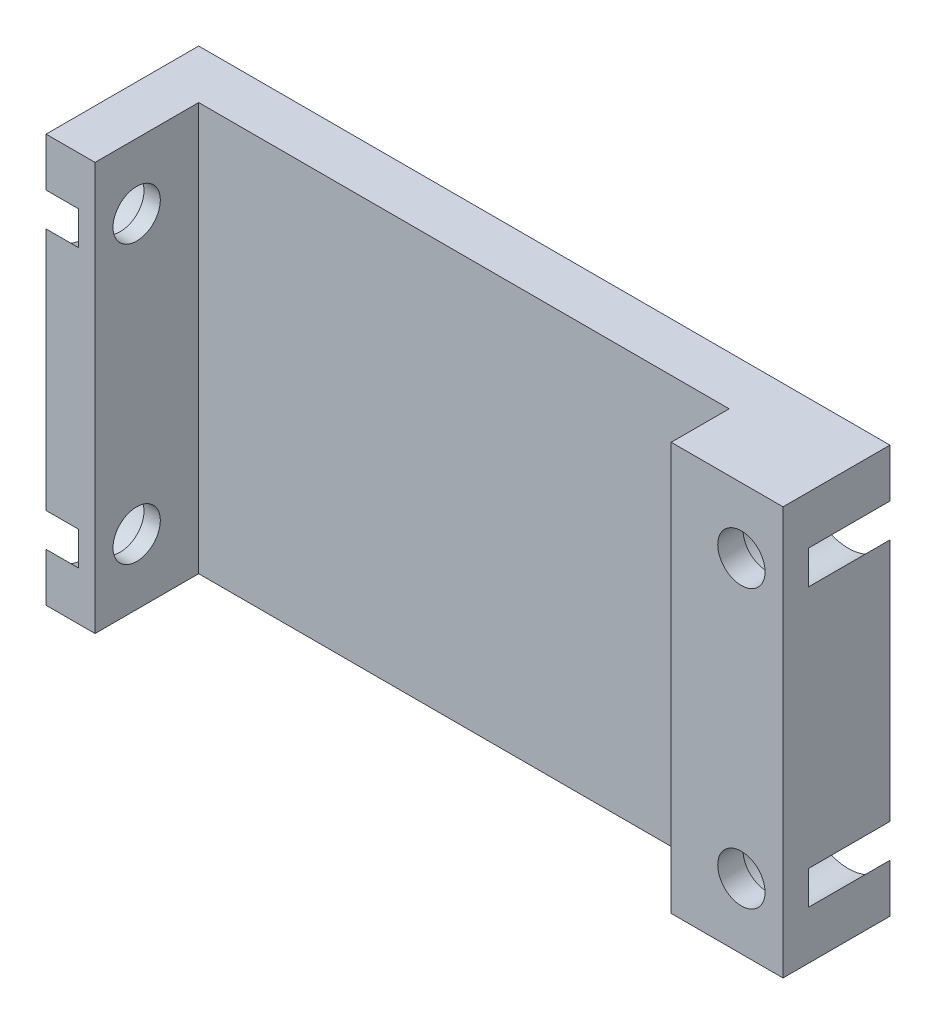
SolidWorks part; units mm, degrees
ref_plane "Plano frontal" through (0, 0, 0) normal (0, 0, 1) x (1, 0, 0)
ref_plane "Plano superior" through (0, 0, 0) normal (0, 1, 0) x (1, 0, 0)
ref_plane "Plano direito" through (0, 0, 0) normal (1, 0, 0) x (0, 0, -1)
sketch "Esboço2" plane through (0, 0, 0) normal (0, 0, 1) x (1, 0, 0)
  line L0 (0, 0) -> (0, -38.6) construction
  line L1 (-1.5, -22.5) -> (5.3501, -22.5)
  line L2 (-1.5, -22.5) -> (-1.5, 2.5)
  line L3 (-1.5, 2.5) -> (5.3501, 2.5)
  line L4 (5.3501, -22.5) -> (5.3501, 2.5)
  line L5 (2.8, -1.5) -> (2.8, 2.5) construction
  line L6 (2.8, -18.5) -> (2.8, -22.5) construction
  dimension "D1" = 0.25
  dimension "D2" = 4
  dimension "D3" = 1.5
extrude "Ressalto-extrusão2" add sketch "Esboço2" against normal offset from surface (3.55 mm away) 1 from offset 0.25 offset beyond the face yes offset against normal yes
sketch "Esboço3" plane through (0, 0, -3.8) normal (0, 0, -1) x (-1, 0, 0)
  line L0 (33.75, 0) -> (33.75, -38.6) construction
  line L1 (-5.3501, 2.5) -> (34, 2.5)
  line L2 (-5.3501, 2.5) -> (-5.3501, -22.5)
  line L3 (-5.3501, -22.5) -> (34, -22.5)
  line L4 (34, 2.5) -> (34, -22.5)
  line L5 (-5.3501, -22.5) -> (1.5, -22.5) construction
  dimension "D1" = 0.25
extrude "Ressalto-extrusão3" add sketch "Esboço3" along normal blind 3
sketch "Esboço4" plane through (-34, 0, 0) normal (-1, 0, 0) x (0, 0, 1)
  line L1 (-6.8, -22.5) -> (2.55, -22.5)
  line L2 (-6.8, -22.5) -> (-6.8, 2.5)
  line L3 (-6.8, 2.5) -> (2.55, 2.5)
  line L4 (2.55, -22.5) -> (2.55, 2.5)
  line L5 (-6.8, 2.5) -> (-3.8, 2.5) construction
  dimension "D1" = 0.25
extrude "Ressalto-extrusão4" add sketch "Esboço4" along normal blind 3
hole_wizard "CBORE for M2.5 SHCS2" positions "3DSketch1" profile "Sketch1" counterbore size "M2.5" standard "ANSI Metric"
sketch3d "3DSketch1"
  circle A0 centre (-33.75, -1.5, 0) radius 1.35 construction
  circle A1 centre (-33.75, -18.5, 0) radius 1.35 construction
  point P0 (-37, -1.5, 0)
  point P7 (-32.4, -1.5, 0)
  point P8 (-37, -18.5, 0)
  point P20 (-32.4, -18.5, 0)
sketch "Sketch1" plane through (-37, -1.5, 0) normal (0, 1, 0) x (0, 0, 1)
  line L0 (0, 0) -> (0, 3.8712)
  line L1 (0, 3.8712) -> (1.45, 3)
  line L2 (1.45, 3) -> (1.45, 2)
  line L3 (1.45, 2) -> (2.75, 2)
  line L4 (2.75, 2) -> (2.75, 0)
  line L5 (2.75, 0) -> (0, 0)
  line L10 (0, 3.8712) -> (-1.45, 3) construction
  line L11 (0, -6.35) -> (0, 107.95) construction
  dimension "Hole Dia." = 2.9
  dimension "Hole Depth" = 3
  dimension "C'Bore Dia." = 5.5
  dimension "C'Bore Depth" = 2
  dimension "Drill Angle" = 118
hole_wizard "CBORE for M2.5 SHCS3" positions "Sketch2" profile "Sketch4" counterbore size "M2.5" standard "ANSI Metric" end condition up to next
sketch "Sketch2" plane through (0, 0, -6.8) normal (0, 0, -1) x (-1, 0, 0)
  circle A0 centre (-2.8, -1.5) radius 1.35 construction
  point P0 (-2.8, -1.5)
  point P6 (-2.8, -18.5)
sketch "Sketch4" plane through (2.8, -1.5, -6.8) normal (1, 0, 0) x (0, 1, 0)
  line L0 (0, 0) -> (0, 6.55)
  line L1 (0, 6.55) -> (1.45, 6.55)
  line L3 (1.45, 6.55) -> (1.45, 5)
  line L4 (1.45, 5) -> (2.75, 5)
  line L5 (2.75, 5) -> (2.75, 0)
  line L7 (2.75, 0) -> (0, 0)
  line L11 (0, -6.35) -> (0, 107.95) construction
  dimension "Thru Hole Dia." = 2.9
  dimension "Thru Hole Depth" = 6.55
  dimension "C'Bore Dia." = 5.5
  dimension "C'Bore Depth" = 5
move or copy body "Corpo-Mover/Copiar1" [suppressed] bodies to move or copy 104
